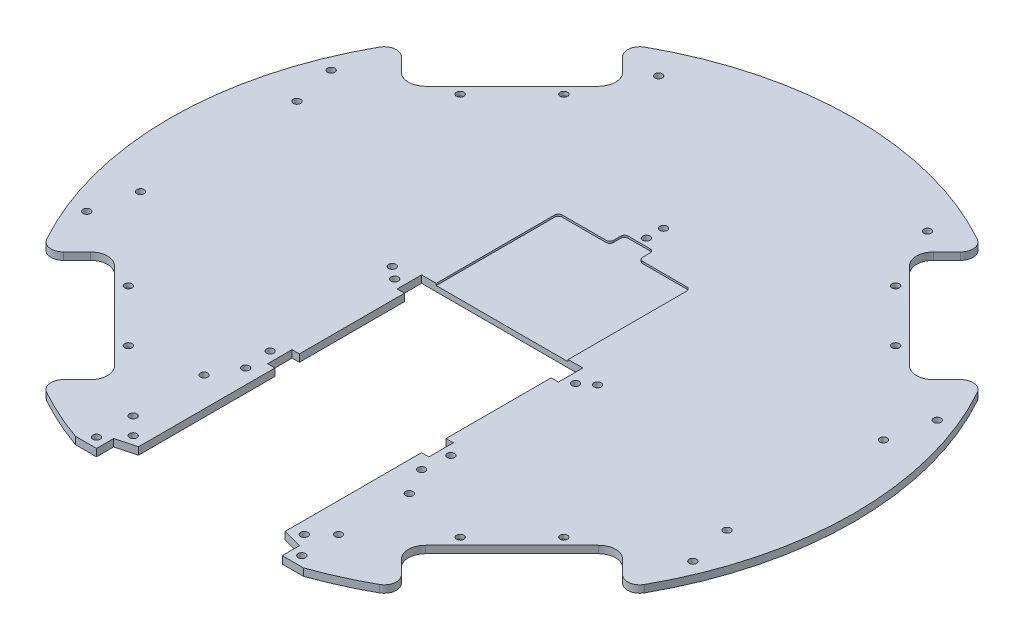
SolidWorks part; units mm, degrees
material "1060 Alloy"
ref_plane "Front Plane" through (0, 0, 0) normal (0, 0, 1) x (1, 0, 0)
ref_plane "Top Plane" through (0, 0, 0) normal (0, 1, 0) x (1, 0, 0)
ref_plane "Right Plane" through (0, 0, 0) normal (1, 0, 0) x (0, 0, -1)
sketch "Sketch1" plane through (0, 0, 0) normal (0, 1, 0) x (1, 0, 0)
  circle A0 centre (0, 0) radius 140
  dimension "D1" = 280
extrude "Boss-Extrude1" add sketch "Sketch1" along normal blind 3
sketch "Sketch7" plane through (0, 3, 0) normal (0, 1, 0) x (1, 0, 0)
  line L0 (-99.0303, -63.6043) -> (-63.6043, -99.0303)
  line L1 (-108.8591, -63.6043) -> (-121.6224, -76.3675)
  line L2 (-63.6043, -108.8591) -> (-76.3675, -121.6224)
  line L3 (-121.6224, -76.3675) -> (-76.3675, -121.6224)
  line L4 (0, 0) -> (-98.9949, -98.9949) construction
  line L7 (0, 0) -> (0, 130) construction
  circle A0 centre (0, 0) radius 140 construction
  arc A1 (-108.8591, -63.6043) -> (-99.0303, -63.6043) centre (-103.9447, -68.5186) cw
  arc A2 (-63.6043, -99.0303) -> (-63.6043, -108.8591) centre (-68.5186, -103.9447) cw
  dimension "D4" = 6.95
  dimension "D1" = 115
  dimension "D2" = 64
  dimension "D3" = 135
extrude "Cut-Extrude4" cut sketch "Sketch7" against normal up to next
sketch "Sketch9" plane through (0, 3, 0) normal (0, 1, 0) x (1, 0, 0)
  line L1 (-63.6043, -99.0303) -> (-99.0303, -63.6043) construction
  line L4 (-108.8591, -63.6043) -> (-119.0017, -73.7469) construction
  circle A0 centre (-89.0955, -67.8823) radius 1.5
  circle A1 centre (-67.8823, -89.0955) radius 1.5
  dimension "D4" = 3
  dimension "D1" = 4
  dimension "D2" = 30
  dimension "D3" = 17
  dimension "D5" = 4
extrude "Cut-Extrude6" cut sketch "Sketch9" against normal up to next
fillet "Fillet1" radius 5 2 edges at (-73.7469, 1.5, 119.0017) (-119.0017, 1.5, 73.7469)
pattern_circular "CirPattern1" count 4 over 360 about axis through (0, 3, 0) along (0, 1, 0) of "Cut-Extrude4", "Fillet1", "Cut-Extrude6"
sketch "Sketch2" plane through (0, 3, 0) normal (0, 1, 0) x (1, 0, 0)
  line L0 (-46.6476, -132) -> (-38, -132)
  line L1 (-30, -122.8564) -> (-30, -67)
  line L2 (-33, -4) -> (33, -4)
  line L3 (30, -67) -> (30, -122.8564)
  line L4 (38, -132) -> (46.6476, -132)
  line L5 (46.6476, -132) -> (46.6476, -140)
  line L6 (46.6476, -140) -> (-46.6476, -140)
  line L7 (-46.6476, -140) -> (-46.6476, -132)
  line L8 (-33, -57) -> (-33, -67)
  line L9 (-33, -67) -> (-30, -67)
  line L10 (33, -57) -> (33, -67)
  line L11 (33, -67) -> (30, -67)
  line L12 (-33, -57) -> (-30, -57)
  line L13 (-30, -57) -> (-30, -14)
  line L14 (-30, -14) -> (-33, -14)
  line L15 (-33, -14) -> (-33, -4)
  line L16 (33, -4) -> (33, -14)
  line L17 (33, -14) -> (30, -14)
  line L18 (30, -14) -> (30, -57)
  line L19 (30, -57) -> (33, -57)
  line L20 (-38, -132) -> (-38, -125)
  line L21 (-38, -125) -> (-30, -122.8564)
  line L22 (38, -132) -> (38, -125)
  line L23 (38, -125) -> (30, -122.8564)
  circle A0 centre (0, 0) radius 140 construction
  dimension "D8" = 3
  dimension "D5" = 63
  dimension "D6" = 66
  dimension "D1" = 8
  dimension "D2" = 65
  dimension "D3" = 60
  dimension "D4" = 16.6476
  dimension "D7" = 10
  dimension "D9" = 76
  dimension "D10" = 7
  dimension "D11" = 105
extrude "Cut-Extrude1" cut sketch "Sketch2" against normal up to next
fillet "Fillet3" radius 1.5 8 edges at (67.8823, 0, 90.5955) (89.0955, 0, 69.3823) (89.0955, 0, -66.3823) (67.8823, 0, -87.5955) (-67.8823, 0, -87.5955) (-89.0955, 0, -66.3823) (-67.8823, 0, 90.5955) (-89.0955, 0, 69.3823)
sketch "Sketch10" plane through (0, 3, 0) normal (0, 1, 0) x (1, 0, 0)
  line L0 (-33, -57) -> (-33, -67) construction
  line L1 (33, -67) -> (33, -57) construction
  line L2 (-33, -67) -> (-30, -67) construction
  line L4 (-30, -14) -> (-33, -14) construction
  line L5 (33, -4) -> (-33, -4) construction
  circle A0 centre (-37, -62) radius 1.5
  circle A1 centre (37, -62) radius 1.5
  circle A2 centre (-37, -11) radius 1.5
  circle A3 centre (37, -11) radius 1.5
  circle A4 centre (-42, -7) radius 1.5
  circle A5 centre (42, -7) radius 1.5
  point P17 (-31.5, -14)
  dimension "D3" = 3
  dimension "D1" = 4
  dimension "D2" = 4
  dimension "D4" = 5
  dimension "D5" = 3
  dimension "D6" = 3
  dimension "D7" = 5
  dimension "D8" = 5
extrude "Cut-Extrude7" cut sketch "Sketch10" against normal up to next
sketch "Sketch13" plane through (0, 3, 0) normal (0, 1, 0) x (1, 0, 0)
  line L0 (-38, -132) -> (-46.6476, -132) construction
  line L1 (-38, -132) -> (-46.6476, -132) construction
  circle A0 centre (-42, -84) radius 1.5
  circle A1 centre (-42, -113) radius 1.5
  circle A2 centre (42, -113) radius 1.5
  circle A3 centre (42, -84) radius 1.5
  dimension "D1" = 3
  dimension "D2" = 19
  dimension "D3" = 48
  dimension "D4" = 42
  dimension "D5" = 42
extrude "Cut-Extrude9" cut sketch "Sketch13" against normal up to next
sketch "Sketch16" plane through (0, 3, 0) normal (0, 1, 0) x (1, 0, 0)
  circle A0 centre (0, 62) radius 1.5
  circle A4 centre (0, 55) radius 1.5
  dimension "D2" = 3
  dimension "D5" = 3
  dimension "D1" = 62
  dimension "D7" = 55
extrude "Cut-Extrude12" cut sketch "Sketch16" against normal up to next
sketch "Sketch17" plane through (0, 3, 0) normal (0, 1, 0) x (1, 0, 0)
  circle A0 centre (-124, 50) radius 1.5
  circle A1 centre (-124, -50) radius 1.5
  circle A2 centre (124, 50) radius 1.5
  circle A3 centre (124, -50) radius 1.5
  dimension "D1" = 3
  dimension "D2" = 50
  dimension "D3" = 50
  dimension "D4" = 124
  dimension "D5" = 124
extrude "Cut-Extrude13" cut sketch "Sketch17" against normal up to next
sketch "Sketch18" plane through (0, 3, 0) normal (0, 1, 0) x (1, 0, 0)
  line L1 (-27, -4) -> (27, -4)
  line L2 (-27, -4) -> (-27, 46)
  line L3 (-27, 46) -> (27, 46)
  line L4 (27, -4) -> (27, 46)
  line L5 (33, -4) -> (-33, -4) construction
  dimension "D1" = 50
  dimension "D2" = 54
  dimension "D3" = 27
extrude "Cut-Extrude14" cut sketch "Sketch18" against normal blind 0.8
sketch "Sketch19" plane through (0, 3, 0) normal (0, 1, 0) x (1, 0, 0)
  line L0 (-38, -125) -> (-38, -132) construction
  line L1 (-38, -132) -> (-46.6476, -132) construction
  line L2 (38, -132) -> (38, -125) construction
  circle A0 centre (-42, -128) radius 1.5
  circle A1 centre (42, -128) radius 1.5
  dimension "D4" = 3
  dimension "D1" = 4
  dimension "D2" = 4
  dimension "D3" = 4
extrude "Cut-Extrude15" cut sketch "Sketch19" against normal up to next
sketch "Sketch20" plane through (0, 3, 0) normal (0, 1, 0) x (1, 0, 0)
  line L0 (27, 46) -> (-27, 46) construction
  line L1 (-6, 46) -> (6, 46)
  line L2 (-6, 46) -> (-6, 52)
  line L3 (-6, 52) -> (6, 52)
  line L4 (6, 46) -> (6, 52)
  circle A0 centre (0, 55) radius 1.5 construction
  dimension "D1" = 12
  dimension "D2" = 6
  dimension "D3" = 3
extrude "Cut-Extrude16" cut sketch "Sketch20" against normal up to surface (0.8 mm away) up to face at (0, 2.2, -21)
fillet "Fillet4" radius 1.5 6 edges at (6, 2.6, -46) (27, 2.6, -46) (-27, 2.6, -46) (-6, 2.6, -46) (6, 2.6, -52) (-6, 2.6, -52)
sketch "Sketch21" plane through (0, 3, 0) normal (0, 1, 0) x (1, 0, 0)
  circle A0 centre (-35, -120) radius 1.5
  circle A1 centre (-36, -73) radius 1.5
  circle A2 centre (35, -120) radius 1.5
  circle A3 centre (36, -73) radius 1.5
  circle A4 centre (-42, -128) radius 1.5 construction
  circle A5 centre (42, -128) radius 1.5 construction
  dimension "D1" = 7
  dimension "D3" = 3
  dimension "D2" = 8
  dimension "D4" = 47
  dimension "D5" = 1
  dimension "D6" = 1
  dimension "D7" = 7
extrude "Cut-Extrude17" cut sketch "Sketch21" against normal up to next
sketch "Sketch22" plane through (0, 3, 0) normal (0, 1, 0) x (1, 0, 0)
  circle A0 centre (120, 32) radius 1.5
  circle A1 centre (120, -32) radius 1.5
  circle A2 centre (-120, 32) radius 1.5
  circle A3 centre (-120, -32) radius 1.5
  dimension "D1" = 3
  dimension "D2" = 120
  dimension "D3" = 32
  dimension "D4" = 32
  dimension "D5" = 120
extrude "Cut-Extrude18" cut sketch "Sketch22" against normal up to next
sketch "Sketch23" plane through (0, 3, 0) normal (0, 1, 0) x (1, 0, 0)
  circle A0 centre (-55, 115) radius 1.5
  circle A1 centre (55, 115) radius 1.5
  dimension "D1" = 3
  dimension "D2" = 55
  dimension "D3" = 115
  dimension "D4" = 55
extrude "Cut-Extrude19" cut sketch "Sketch23" against normal up to next
